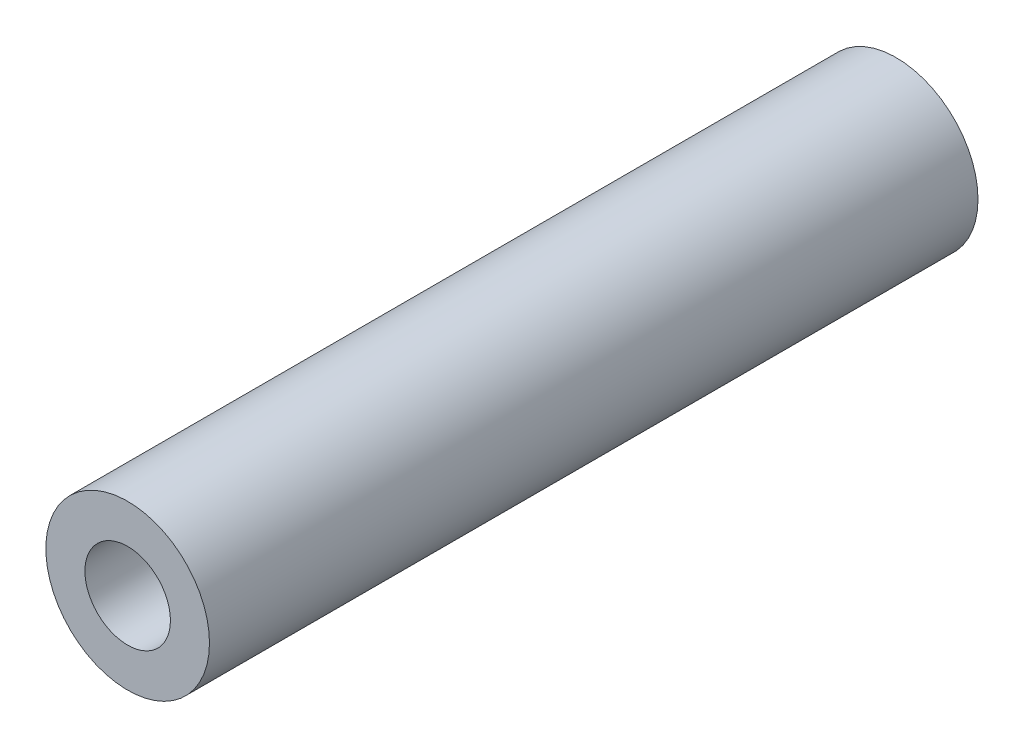
SolidWorks part; units mm, degrees
ref_plane "Front Plane" through (0, 0, 0) normal (0, 0, 1) x (1, 0, 0)
ref_plane "Top Plane" through (0, 0, 0) normal (0, 1, 0) x (1, 0, 0)
ref_plane "Right Plane" through (0, 0, 0) normal (1, 0, 0) x (0, 0, -1)
sketch "Sketch1" plane through (0, 0, 0) normal (0, 0, 1) x (1, 0, 0)
  circle A0 centre (0, 0) radius 4.7625
  circle A1 centre (0, 0) radius 2.4892
  dimension "D1" = 4.9784
  dimension "D2" = 9.525
extrude "Boss-Extrude1" add sketch "Sketch1" along normal mid plane 44.7345 contours A1 | A0 region at (0, 0, 0)
